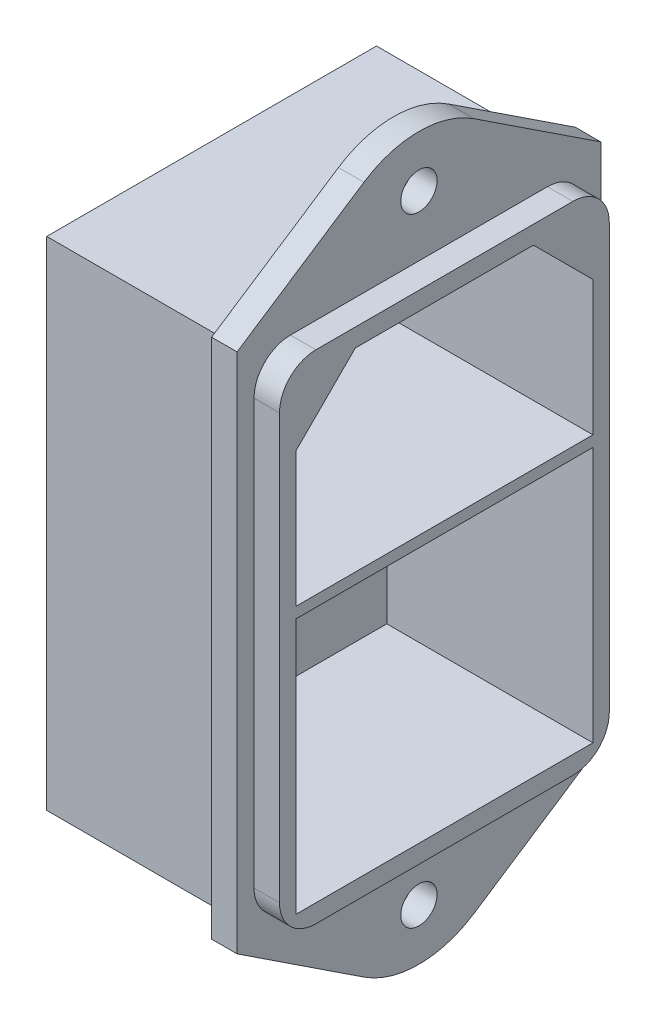
SolidWorks part; units mm, degrees
ref_plane "Front Plane" through (0, 0, 0) normal (0, 0, 1) x (1, 0, 0)
ref_plane "Top Plane" through (0, 0, 0) normal (0, 1, 0) x (1, 0, 0)
ref_plane "Right Plane" through (0, 0, 0) normal (1, 0, 0) x (0, 0, -1)
sketch "Sketch1" plane through (0, 0, 0) normal (1, 0, 0) x (0, 0, -1)
  line L0 (0, 0) -> (0, 3) construction
  line L1 (-13.6, 20.5) -> (13.6, 20.5)
  line L2 (-13.6, 20.5) -> (-13.6, -20.5)
  line L3 (-13.6, -20.5) -> (13.6, -20.5)
  line L4 (13.6, 20.5) -> (13.6, -20.5)
  line L5 (-13.6, 20.5) -> (13.6, -20.5) construction
  line L6 (-13.6, -20.5) -> (13.6, 20.5) construction
  line L7 (-12.25, 3) -> (12.25, 3)
  line L8 (12.25, 3) -> (12.25, 14.1)
  line L9 (12.25, 14.1) -> (7.35, 19)
  line L10 (7.35, 19) -> (-7.35, 19)
  line L11 (-7.35, 19) -> (-12.25, 14.1)
  line L12 (-12.25, 14.1) -> (-12.25, 3)
  line L13 (0, 0) -> (0, -20.5) construction
  line L14 (-15, 21.5) -> (-4.5375, 28.3901)
  line L15 (-12.25, 2.1) -> (12.25, 2.1)
  line L16 (-12.25, 2.1) -> (-12.25, -19)
  line L17 (-12.25, -19) -> (12.25, -19)
  line L18 (12.25, 2.1) -> (12.25, -19)
  line L19 (-12.25, 2.1) -> (12.25, -19) construction
  line L20 (-12.25, -19) -> (12.25, 2.1) construction
  line L21 (-15, 21.5) -> (15, 21.5)
  line L22 (-15, 21.5) -> (-15, -21.5)
  line L23 (-15, -21.5) -> (15, -21.5)
  line L24 (15, 21.5) -> (15, -21.5)
  line L25 (-15, 21.5) -> (15, -21.5) construction
  line L26 (-15, -21.5) -> (15, 21.5) construction
  line L27 (4.5375, 28.3901) -> (15, 21.5)
  line L28 (0, 0) -> (15, 0) construction
  line L29 (0, 29.75) -> (0, 21.5) construction
  line L30 (0, -29.75) -> (0, -21.5) construction
  line L31 (4.5375, -28.3901) -> (15, -21.5)
  line L32 (-15, -21.5) -> (15, -21.5)
  line L33 (-15, -21.5) -> (-4.5375, -28.3901)
  arc A0 (-4.5375, 28.3901) -> (4.5375, 28.3901) centre (0, 21.5) cw
  circle A1 centre (0, 25.5) radius 1.5
  circle A2 centre (0, -25.5) radius 1.5
  arc A3 (-4.5375, -28.3901) -> (4.5375, -28.3901) centre (0, -21.5) ccw
  point P0 (0, 0)
  point P11 (0, 3)
  point P15 (0, -8.45)
  point P32 (0, 29.75)
  dimension "D13" = 3
  dimension "D1" = 27.2
  dimension "D2" = 41
  dimension "D3" = 16
  dimension "D4" = 24.5
  dimension "D5" = 11.1
  dimension "D6" = 1.5
  dimension "D7" = 21.1
  dimension "D8" = 24.5
  dimension "D9" = 1.5
  dimension "D10" = 43
  dimension "D11" = 30
  dimension "D12" = 8.25
  dimension "D14" = 4
extrude "Boss-Extrude1" add sketch "Sketch1" along normal blind 2.1 contours A0 L14 L21 L27 A1 | L24 L21 L22 L23 L1 L4 L3 L2 | L4 L1 L2 L3 L12 L11 L10 L9 L8 L7 L15 L18 L17 L16 | L33 A3 L31 L23 A2 region at (0, 20.008, 0) region at (0, 24.6852, 9.5976) region at (0, 20.9757, 0) region at (0, -21.8111, 0)
extrude "Boss-Extrude2" add sketch "Sketch1<3>" along normal blind 2.1 from surface contours L4 L1 L2 L3 L12 L11 L10 L9 L8 L7 L15 L18 L17 L16 region at (0, 20.008, 0) starting at face at (2.1, 25.5, -1.5)
sketch "Sketch1<3>" plane through (0, 0, 0) normal (1, 0, 0) x (0, 0, -1) same geometry as "Sketch1"
fillet "Fillet1" radius 3 4 edges at (3.15, 20.5, 13.6) (3.15, 20.5, -13.6) (3.15, -20.5, -13.6) (3.15, -20.5, 13.6)
extrude "Boss-Extrude3" add sketch "Sketch1<4>" against normal blind 15 contours L4 L1 L2 L3 L12 L11 L10 L9 L8 L7 L15 L18 L17 L16 region at (0, 20.008, 0)
sketch "Sketch1<4>" plane through (0, 0, 0) normal (1, 0, 0) x (0, 0, -1) same geometry as "Sketch1"
extrude "Boss-Extrude4" add sketch "Sketch1<5>" along normal offset from surface (2.2 mm away) 17 from surface contours L11 L12 L7 L8 L9 L10 | L18 L15 L16 L17 region at (0, 10.5846, 0) region at (0, -8.45, 0) up to face at (4.2, 12.0333, 0) starting at face at (-15, 12.0333, 0)
sketch "Sketch1<5>" plane through (0, 0, 0) normal (1, 0, 0) x (0, 0, -1) same geometry as "Sketch1"
